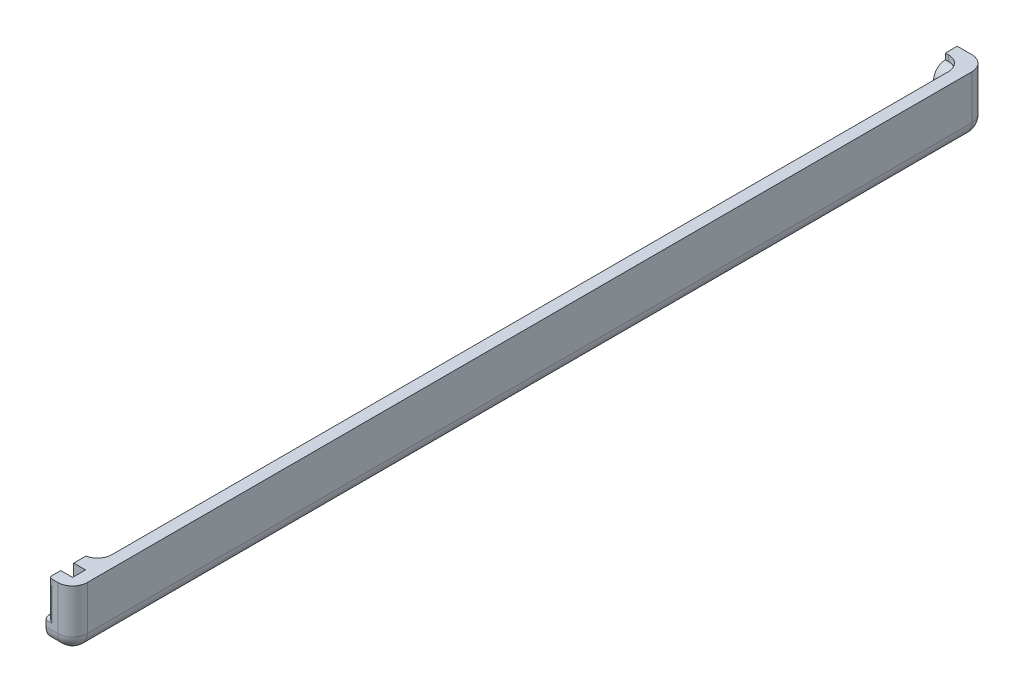
SolidWorks part; units mm, degrees
ref_plane "Front Plane" through (0, 0, 0) normal (0, 0, 1) x (1, 0, 0)
ref_plane "Top Plane" through (0, 0, 0) normal (0, 1, 0) x (1, 0, 0)
ref_plane "Right Plane" through (0, 0, 0) normal (1, 0, 0) x (0, 0, -1)
sketch "Sketch1" plane through (0, 0, 0) normal (0, 1, 0) x (1, 0, 0)
  line L1 (-19.5, 77.5) -> (19.5, 77.5)
  line L2 (-19.5, 77.5) -> (-19.5, -77.5)
  line L3 (-19.5, -77.5) -> (19.5, -77.5)
  line L4 (19.5, 77.5) -> (19.5, -77.5)
  line L5 (-19.5, 77.5) -> (19.5, -77.5) construction
  line L6 (-19.5, -77.5) -> (19.5, 77.5) construction
  point P0 (0, 0)
  dimension "D1" = 39
  dimension "D2" = 155
extrude "Boss-Extrude1" add sketch "Sketch1" along normal blind 2
sketch "Sketch2" plane through (0, 2, 0) normal (0, 1, 0) x (1, 0, 0)
  line L0 (-17.5, -75.5) -> (-17.5, -77.5)
  line L1 (-19.5, 77.5) -> (19.5, 77.5)
  line L2 (-19.5, 77.5) -> (-19.5, -77.5)
  line L3 (-19.5, -77.5) -> (19.5, -77.5)
  line L4 (19.5, 77.5) -> (19.5, -77.5)
  line L5 (-17.5, 75.5) -> (17.5, 75.5)
  line L6 (-17.5, 75.5) -> (-17.5, -75.5)
  line L7 (-17.5, -75.5) -> (17.5, -75.5)
  line L8 (17.5, 75.5) -> (17.5, -75.5)
  line L9 (-17.5, 75.5) -> (17.5, -75.5) construction
  line L10 (-17.5, -75.5) -> (17.5, 75.5) construction
  line L11 (17.5, -75.5) -> (17.5, -77.5)
  point P6 (0, 0)
  line M9 (19.5, -77.5) -> (19.5, 77.5)
  line M10 (19.5, 77.5) -> (-19.5, 77.5)
  line M11 (-19.5, 77.5) -> (-19.5, -77.5)
  line M12 (-19.5, -77.5) -> (19.5, -77.5)
  dimension "D1" = 2
  dimension "D2" = 2
extrude "Boss-Extrude2" add sketch "Sketch2" along normal blind 38 contours L8 L11 L3 L0 L6 L5 M9 M10 M11 M12 region at (-19.0983, 2, 76.5)
sketch "Sketch3" plane through (0, 2, 0) normal (0, 1, 0) x (1, 0, 0)
  line L0 (-17.5, 75.5) -> (-17.5, -77.5) construction
  line L1 (-17.5, -77.5) -> (-15.5, -77.5)
  line L2 (-17.5, -77.5) -> (-17.5, -75.5)
  line L3 (-17.5, -75.5) -> (-15.5, -75.5)
  line L4 (-15.5, -77.5) -> (-15.5, -75.5)
  line L5 (-17.5, -73.3) -> (-15.5, -73.3)
  line L6 (-17.5, -73.3) -> (-17.5, -71.3)
  line L7 (-17.5, -71.3) -> (-15.5, -71.3)
  line L8 (-15.5, -73.3) -> (-15.5, -71.3)
  line L9 (17.5, 75.5) -> (17.5, -77.5) construction
  line L10 (17.5, -77.5) -> (15.5, -77.5)
  line L11 (17.5, -77.5) -> (17.5, -75.5)
  line L12 (17.5, -75.5) -> (15.5, -75.5)
  line L13 (15.5, -77.5) -> (15.5, -75.5)
  line L14 (17.5, -73.3) -> (15.5, -73.3)
  line L15 (17.5, -73.3) -> (17.5, -71.3)
  line L16 (17.5, -71.3) -> (15.5, -71.3)
  line L17 (15.5, -73.3) -> (15.5, -71.3)
  line L18 (15.5, -75.5) -> (15.5, -73.3) construction
  line L19 (-15.5, -73.3) -> (15.5, -73.3) construction
  line L20 (-15.5, -75.5) -> (-15.5, -73.3) construction
  line L21 (-15.5, -75.5) -> (15.5, -75.5) construction
  line L22 (15.5, -71.3) -> (-15.5, -71.3) construction
  dimension "D1" = 2
  dimension "D2" = 2
  dimension "D3" = 2.2
  dimension "D4" = 2
extrude "Boss-Extrude3" add sketch "Sketch3" along normal up to surface (38 mm away) up to face at (0, 40, 0.5)
sketch "Sketch4" plane through (0, 0, -75.5) normal (0, 0, 1) x (1, 0, 0)
  line L0 (-17.5, 40) -> (-15.5, 40)
  line L1 (-17.5, 40) -> (17.5, 40) construction
  line L2 (-15.5, 40) -> (-15.5, 38)
  line L3 (-15.5, 38) -> (-17.5, 38)
  line L5 (-17.5, 38) -> (-17.5, 40)
  line L7 (-17.5, 40) -> (-17.5, 2) construction
  line L8 (-15.5, 33.8) -> (-17.5, 31.8)
  line L9 (-17.5, 31.8) -> (-17.5, 35.8)
  line L10 (-15.5, 33.8) -> (-15.5, 35.8)
  line L11 (-15.5, 35.8) -> (-17.5, 35.8)
  line L12 (0, 0) -> (0, 40) construction
  line L13 (15.5, 35.8) -> (17.5, 35.8)
  line L14 (15.5, 33.8) -> (15.5, 35.8)
  line L15 (17.5, 31.8) -> (17.5, 35.8)
  line L16 (15.5, 33.8) -> (17.5, 31.8)
  line L17 (17.5, 38) -> (17.5, 40)
  line L18 (15.5, 38) -> (17.5, 38)
  line L19 (15.5, 40) -> (15.5, 38)
  line L20 (17.5, 40) -> (15.5, 40)
  dimension "D1" = 2
  dimension "D2" = 2
  dimension "D3" = 45
  dimension "D4" = 2.2
  dimension "D5" = 2
extrude "Boss-Extrude4" add sketch "Sketch4" along normal up to surface (153 mm away) up to face at (0, 20.5, 77.5)
sketch "Sketch5" plane through (0, 2, 0) normal (0, 1, 0) x (1, 0, 0)
  line L1 (-15.5, -77.5) -> (15.5, -77.5)
  line L2 (-15.5, -77.5) -> (-15.5, -75.5)
  line L3 (-15.5, -75.5) -> (15.5, -75.5)
  line L4 (15.5, -77.5) -> (15.5, -75.5)
  line L5 (-15.5, -71.3) -> (15.5, -71.3)
  line L6 (-15.5, -71.3) -> (-15.5, -73.3)
  line L7 (-15.5, -73.3) -> (15.5, -73.3)
  line L8 (15.5, -71.3) -> (15.5, -73.3)
sketch "Sketch6" plane through (0, 0, -75.5) normal (0, 0, 1) x (1, 0, 0)
  line L0 (-17.5, 38) -> (-15.5, 38) construction
  line L1 (-17.5, 38) -> (17.5, 38)
  line L2 (-17.5, 38) -> (-17.5, 35.8)
  line L3 (-17.5, 35.8) -> (17.5, 35.8)
  line L4 (17.5, 38) -> (17.5, 35.8)
  line L5 (-17.5, 38) -> (-17.5, 35.8) construction
  line L6 (-15.5, 35.8) -> (-17.5, 35.8) construction
extrude "Cut-Extrude1" cut sketch "Sketch6" along normal through all
sketch "Sketch7" plane through (0, 2, 0) normal (0, 1, 0) x (1, 0, 0)
  line L1 (-17.5, -75.5) -> (17.5, -75.5)
  line L2 (-17.5, -75.5) -> (-17.5, -73.3)
  line L3 (-17.5, -73.3) -> (17.5, -73.3)
  line L4 (17.5, -75.5) -> (17.5, -73.3)
extrude "Cut-Extrude2" cut sketch "Sketch7" along normal through all
extrude "Boss-Extrude5" add sketch "Sketch5" along normal blind 2
sketch "Sketch8" plane through (0, 0, 0) normal (1, 0, 0) x (0, 0, -1)
  line L0 (75.5, 40) -> (73.5, 40)
  line L1 (-73.3, 40) -> (75.5, 40) construction
  line L2 (73.5, 40) -> (73.5, 38)
  line L3 (-73.3, 38) -> (75.5, 38) construction
  line L4 (73.5, 38) -> (75.5, 38)
  line L5 (75.5, 38) -> (75.5, 40)
  line L6 (75.5, 35.8) -> (73.5, 35.8)
  line L7 (-73.3, 35.8) -> (75.5, 35.8) construction
  line L8 (73.5, 35.8) -> (73.5, 33.8)
  line L9 (-71.3, 33.8) -> (75.5, 33.8) construction
  line L10 (73.5, 33.8) -> (75.5, 31.8)
  line L11 (75.5, 31.8) -> (75.5, 35.8)
  dimension "D1" = 2
extrude "Boss-Extrude6" add sketch "Sketch8" along normal up to surface and the other way up to surface up to face at (17.5, 16.9, -2.1) other way up to face at (-17.5, 16.9, -2.1)
sketch "Sketch10" plane through (-17.5, 0, 0) normal (1, 0, 0) x (0, 0, -1)
  line L1 (-75.5, 35.8) -> (-77.5, 35.8)
  line L2 (-75.5, 35.8) -> (-75.5, 38)
  line L3 (-75.5, 38) -> (-77.5, 38)
  line L4 (-77.5, 35.8) -> (-77.5, 38)
  line L5 (-73.3, 40) -> (-75.5, 40)
  line L6 (-73.3, 40) -> (-73.3, 38)
  line L7 (-73.3, 38) -> (-75.5, 38)
  line L8 (-75.5, 40) -> (-75.5, 38)
  line M1 (-75.5, 40) -> (-75.5, 38)
  line M2 (-75.5, 38) -> (-77.5, 38)
  line M3 (-77.5, 38) -> (-77.5, 35.8)
  line M4 (-77.5, 35.8) -> (-75.5, 35.8)
  line M11 (-73.3, 38) -> (-73.3, 40)
  line M12 (-73.3, 40) -> (-75.5, 40)
extrude "Boss-Extrude8" add sketch "Sketch10" along normal up to surface (2 mm away) contours L2 M4 M2 M3 | L7 M11 M12 M1 region at (-17.5, 39, 74.4) region at (-17.5, 36.9, 76.5) up to face at (-15.5, 39, -0.1)
sketch "Sketch11" plane through (17.5, 0, 0) normal (-1, 0, 0) x (0, 0, 1)
  line L1 (75.5, 35.8) -> (77.5, 35.8)
  line L2 (75.5, 35.8) -> (75.5, 38)
  line L3 (75.5, 38) -> (77.5, 38)
  line L4 (77.5, 35.8) -> (77.5, 38)
  line L5 (73.3, 40) -> (75.5, 40)
  line L6 (73.3, 40) -> (73.3, 38)
  line L7 (73.3, 38) -> (75.5, 38)
  line L8 (75.5, 40) -> (75.5, 38)
  line M2 (75.5, 35.8) -> (77.5, 35.8)
  line M3 (77.5, 35.8) -> (77.5, 38)
  line M4 (77.5, 38) -> (75.5, 38)
  line M5 (75.5, 38) -> (75.5, 40)
  line M6 (75.5, 40) -> (73.3, 40)
  line M7 (73.3, 40) -> (73.3, 38)
extrude "Boss-Extrude9" add sketch "Sketch11" along normal up to surface (2 mm away) contours L2 M2 M3 M4 | L7 M7 M5 M6 region at (17.5, 36.9, 76.5) region at (17.5, 39, 74.4) up to face at (15.5, 39, -0.1)
fillet "Fillet2" radius 2.5 17 edges at (-17.5, 16.9, 71.3) (17.5, 16.9, 71.3) (19.5, 20, 77.5) (-19.5, 20, 77.5) (-19.5, 20, -77.5) (-17.5, 16.9, -75.5) (17.5, 16.9, -75.5) (19.5, 20, -77.5) (-19.5, 40, 0) (0, 40, -77.5) (19.5, 40, 0) (0, 0, -77.5) (0, 0, 77.5) (-19.5, 0, 0) (19.5, 0, 0) (-17.5, 40, 77.5) (17.5, 40, 77.5)
sketch "Sketch13" plane through (0, 0, -77.5) normal (0, 0, -1) x (-1, 0, 0)
  line L0 (15.5, 37.5) -> (15.5, 4) construction
  line L1 (-15.5, 7) -> (15.5, 7)
  line L2 (-15.5, 7) -> (-15.5, 4)
  line L3 (-15.5, 4) -> (15.5, 4)
  line L4 (15.5, 7) -> (15.5, 4)
  dimension "D1" = 3
sketch "Sketch14" plane through (0, 0, -75.5) normal (0, 0, 1) x (1, 0, 0)
  line L1 (-18.25, 9) -> (18.25, 9)
  line L2 (-18.25, 9) -> (-18.25, 1.25)
  line L3 (-18.25, 1.25) -> (18.25, 1.25)
  line L4 (18.25, 9) -> (18.25, 1.25)
  line L5 (15.5, 7) -> (-15.5, 7) construction
  line L7 (17, 0) -> (17, 2.5) construction
  line L8 (19.5, 2.5) -> (17, 2.5) construction
  line L10 (-19.5, 2.5) -> (-17, 2.5) construction
  point P20 (17, 1.25)
  point P23 (18.25, 2.5)
  point P26 (-18.25, 2.5)
  dimension "D1" = 2
extrude "Boss-Extrude10" add sketch "Sketch14" along normal blind 2
extrude "Cut-Extrude4" cut sketch "Sketch13" against normal blind 2
fillet "Fillet3" radius 2 1 edges at (0, 9, -73.5)
fillet "Fillet4" radius 0.5 12 edges at (0, 4, -77.5) (0, 7, -77.5) (15.5, 7, -76.5) (15.5, 4, -76.5) (15.5, 5.5, -77.5) (-15.5, 4, -76.5) (-15.5, 7, -76.5) (-15.5, 5.5, -77.5) (0, 7, -75.5) (-15.5, 5.5, -75.5) (0, 4, -75.5) (15.5, 5.5, -75.5)
sketch "Sketch15" plane through (0, 0, 0) normal (0, -1, 0) x (1, 0, 0)
  line L0 (0, 77.5) -> (0, 0) construction
  line L1 (-17, 77.5) -> (17, 77.5) construction
  line L2 (0, 0) -> (0, -77.5) construction
  line L4 (17, -77.5) -> (-17, -77.5) construction
  circle A0 centre (0, 38.75) radius 5.1
  circle A1 centre (0, -38.75) radius 5.1
  dimension "D1" = 10.2
extrude "Cut-Extrude5" cut sketch "Sketch15" against normal through all
sketch "Sketch16" plane through (0, 2, 0) normal (0, 1, 0) x (1, 0, 0)
  circle A0 centre (0, 38.75) radius 7.1
  circle A1 centre (0, -38.75) radius 7.1
  circle A2 centre (0, 38.75) radius 5.1 construction
  dimension "D1" = 2
extrude "Boss-Extrude11" add sketch "Sketch16" along normal blind 1
fillet "Fillet5" radius 0.5 4 edges at (0, 2, 45.85) (0, 2, -31.65) (0, 3, 45.85) (0, 3, -31.65)
sketch "Sketch12" plane through (0, 0, -75.5) normal (0, 0, 1) x (1, 0, 0)
  line L0 (0, 0) -> (0, 40) construction
  line L1 (15.5, 40) -> (-15.5, 40) construction
  line L2 (0, 20) -> (-10, 20)
  line L3 (0, 20) -> (-9.0097, 15.6612)
  line L4 (0, 20) -> (-6.2349, 12.1817)
  line L5 (0, 20) -> (-2.2252, 10.2507)
  line L6 (0, 20) -> (2.2252, 10.2507)
  line L7 (0, 20) -> (6.2349, 12.1817)
  line L8 (0, 20) -> (9.0097, 15.6612)
  line L9 (0, 20) -> (10, 20)
  line L10 (0, 20) -> (9.0097, 24.3388)
  line L11 (0, 20) -> (6.2349, 27.8183)
  line L12 (0, 20) -> (2.2252, 29.7493)
  line L13 (0, 20) -> (-2.2252, 29.7493)
  line L14 (0, 20) -> (-6.2349, 27.8183)
  line L15 (0, 20) -> (-9.0097, 24.3388)
  circle A0 centre (0, 20) radius 10
  circle A1 centre (0, 20) radius 7.5
  circle A2 centre (0, 20) radius 5
  circle A3 centre (0, 20) radius 2.5
  point P26 (0, 20)
  dimension "D1" = 20
  dimension "D2" = 2.5
  dimension "D3" = 2.5
  dimension "D4" = 2.5
  dimension "D5" = 14
extrude "Cut-Extrude3" cut sketch "Sketch12" against normal through all contours A1 L6 A0 L7 | A1 L4 A0 L5 | A1 L2 A0 L3 | A1 L14 A0 L15 | A1 L0 A0 L13 | L0 A1 L12 A0 | A1 L10 A0 L11 | A1 L8 A0 L9 | A3 L8 A2 L9 | A3 L10 A2 L11 | L0 A3 L12 A2 | A3 L0 A2 L13 | A3 L14 A2 L15 | A3 L2 A2 L3 | A3 L4 A2 L5 | A3 L6 A2 L7 region at (-3.7903, 12.1293, -75.5) region at (3.7903, 12.1293, -75.5) region at (-1.6732, 16.5256, -75.5) region at (1.6732, 16.5256, -75.5) region at (-8.5168, 18.0561, -75.5) region at (8.5168, 18.0561, -75.5) region at (-0.4345, 23.8563, -75.5) region at (0.4345, 23.8563, -75.5) region at (-3.7596, 19.1419, -75.5) region at (3.7596, 19.1419, -75.5) region at (3.015, 22.4044, -75.5) region at (-3.015, 22.4044, -75.5) region at (-6.8299, 25.4467, -75.5) region at (6.8299, 25.4467, -75.5) region at (-0.9843, 28.7358, -75.5) region at (0.9843, 28.7358, -75.5)
fillet "Fillet6" radius 0.4 112 edges at (5.4555, 26.841, -77.5) (7.8183, 26.2349, -77.5) (7.8835, 23.7965, -77.5) (5.8637, 24.6762, -77.5) (3.75, 20, -77.5) (4.8746, 18.8874, -77.5) (3.3786, 18.3729, -77.5) (2.4373, 19.4437, -77.5) (-1.9471, 28.5306, -77.5) (0, 30, -77.5) (1.9471, 28.5306, -77.5) (0, 27.5, -77.5) (-7.8835, 16.2035, -77.5) (-9.7493, 17.7748, -77.5) (-8.75, 20, -77.5) (-7.312, 18.3311, -77.5) (2.3381, 17.0681, -77.5) (2.1694, 15.4952, -77.5) (0.8345, 16.344, -77.5) (1.0847, 17.7476, -77.5) (-0.8345, 16.344, -77.5) (-2.1694, 15.4952, -77.5) (-2.3381, 17.0681, -77.5) (-1.0847, 17.7476, -77.5) (5.4555, 13.159, -77.5) (4.3388, 10.9903, -77.5) (1.9471, 11.4694, -77.5) (3.2541, 13.2427, -77.5) (0, 22.5, -77.5) (-0.8345, 23.656, -77.5) (0, 25, -77.5) (0.8345, 23.656, -77.5) (-3.3786, 21.6271, -77.5) (-3.9092, 23.1174, -77.5) (-2.3381, 22.9319, -77.5) (-1.9546, 21.5587, -77.5) (-3.3786, 18.3729, -77.5) (-4.8746, 18.8874, -77.5) (-3.75, 20, -77.5) (-2.4373, 19.4437, -77.5) (-1.9471, 11.4694, -77.5) (-4.3388, 10.9903, -77.5) (-5.4555, 13.159, -77.5) (-3.2541, 13.2427, -77.5) (-7.8835, 23.7965, -77.5) (-7.8183, 26.2349, -77.5) (-5.4555, 26.841, -77.5) (-5.8637, 24.6762, -77.5) (2.3381, 22.9319, -77.5) (3.9092, 23.1174, -77.5) (3.3786, 21.6271, -77.5) (1.9546, 21.5587, -77.5) (8.75, 20, -77.5) (9.7493, 17.7748, -77.5) (7.8835, 16.2035, -77.5) (7.312, 18.3311, -77.5) (7.8835, 23.7965, -75.5) (7.8183, 26.2349, -75.5) (5.4555, 26.841, -75.5) (5.8637, 24.6762, -75.5) (3.3786, 18.3729, -75.5) (4.8746, 18.8874, -75.5) (3.75, 20, -75.5) (2.4373, 19.4437, -75.5) (1.9471, 28.5306, -75.5) (0, 30, -75.5) (-1.9471, 28.5306, -75.5) (0, 27.5, -75.5) (-8.75, 20, -75.5) (-9.7493, 17.7748, -75.5) (-7.8835, 16.2035, -75.5) (-7.312, 18.3311, -75.5) (0.8345, 16.344, -75.5) (2.1694, 15.4952, -75.5) (2.3381, 17.0681, -75.5) (1.0847, 17.7476, -75.5) (-2.3381, 17.0681, -75.5) (-2.1694, 15.4952, -75.5) (-0.8345, 16.344, -75.5) (-1.0847, 17.7476, -75.5) (1.9471, 11.4694, -75.5) (4.3388, 10.9903, -75.5) (5.4555, 13.159, -75.5) (3.2541, 13.2427, -75.5) (0, 22.5, -75.5) (0.8345, 23.656, -75.5) (0, 25, -75.5) (-0.8345, 23.656, -75.5) (-2.3381, 22.9319, -75.5) (-3.9092, 23.1174, -75.5) (-3.3786, 21.6271, -75.5) (-1.9546, 21.5587, -75.5) (-3.75, 20, -75.5) (-4.8746, 18.8874, -75.5) (-3.3786, 18.3729, -75.5) (-2.4373, 19.4437, -75.5) (-5.4555, 13.159, -75.5) (-4.3388, 10.9903, -75.5) (-1.9471, 11.4694, -75.5) (-3.2541, 13.2427, -75.5) (-5.4555, 26.841, -75.5) (-7.8183, 26.2349, -75.5) (-7.8835, 23.7965, -75.5) (-5.8637, 24.6762, -75.5) (3.3786, 21.6271, -75.5) (3.9092, 23.1174, -75.5) (2.3381, 22.9319, -75.5) (7.8835, 16.2035, -75.5) (9.7493, 17.7748, -75.5) (8.75, 20, -75.5) (7.312, 18.3311, -75.5) (1.9546, 21.5587, -75.5)
fillet "Fillet7" radius 0.5 8 edges at (15.5, 40, 0.75) (15.5, 39.2678, 76.7678) (-15.5, 40, 0.75) (-15.5, 39.2678, 76.7678) (0, 40, -73.5) (15.5, 20.75, 77.5) (-15.5, 20.75, 77.5) (0, 4, 77.5)
sketch "Sketch17" plane through (0, 0, 0) normal (0, -1, 0) x (1, 0, 0)
  line L0 (-17, -77.5) -> (-17, 70.3)
  line L1 (-17, -77.5) -> (17, -77.5)
  line L2 (17, -77.5) -> (17, 70.3)
  line L3 (17, -75) -> (17, 75) construction
  line L5 (17, 70.3) -> (15, 71.3)
  line L6 (15, 71.3) -> (15, 77.5)
  line L7 (15, 77.5) -> (-15, 77.5)
  line L8 (-15, 77.5) -> (-15, 71.3)
  line L9 (-15, 71.3) -> (-17, 70.3)
  line L10 (-17, 75) -> (-17, -75) construction
  line L12 (-15, 71.3) -> (15, 71.3) construction
  line L13 (17, 70.3) -> (-17, 70.3) construction
  line L14 (0, 71.3) -> (0, 77.5) construction
  line L15 (-17, 77.5) -> (17, 77.5) construction
  arc A0 (-19.5, -75) -> (-17, -77.5) centre (-17, -75) ccw construction
  dimension "D1" = 1
  dimension "D2" = 30
  dimension "D3" = 6.2
extrude "Cut-Extrude6" cut sketch "Sketch17" against normal blind 6
sketch "Sketch18" plane through (0, 0, 0) normal (0, 0, 1) x (1, 0, 0)
  line L0 (15, 9) -> (-15, 9) construction
  line L1 (-14.5, 9) -> (14.5, 9)
  line L2 (-14.5, 9) -> (-14.5, 6)
  line L3 (-14.5, 6) -> (14.5, 6)
  line L4 (14.5, 9) -> (14.5, 6)
  line L5 (-17, 6) -> (17, 6) construction
  line L6 (0, 6) -> (0, 0) construction
  dimension "D1" = 29
extrude "Cut-Extrude8" cut sketch "Sketch18" against normal through all
sketch "Sketch20" plane through (0, 0, 0) normal (0, 0, 1) x (1, 0, 0)
  line L0 (-16, 40) -> (16, 40) construction
  line L1 (-19.5, 40) -> (-14.5, 40)
  line L2 (-19.5, 40) -> (-19.5, 0)
  line L3 (-19.5, 0) -> (-14.5, 0)
  line L4 (-14.5, 40) -> (-14.5, 0)
  line L5 (-14.5, 6) -> (14.5, 6)
  line L6 (-14.5, 6) -> (-14.5, 40)
  line L7 (-14.5, 40) -> (14.5, 40)
  line L8 (14.5, 6) -> (14.5, 40)
  line L9 (14.5, 40) -> (19.5, 40)
  line L10 (14.5, 40) -> (14.5, 0)
  line L11 (14.5, 0) -> (19.5, 0)
  line L12 (19.5, 40) -> (19.5, 0)
  line L13 (-15, 0) -> (-17, 0) construction
  line L14 (-19.5, 2.5) -> (-19.5, 37.5) construction
  line L15 (17, 0) -> (15, 0) construction
  line L16 (19.5, 37.5) -> (19.5, 2.5) construction
extrude "Cut-Extrude11" cut sketch "Sketch20" against normal through all both and the other way through all contours L5 L8 L7 L4 | L1 L2 L3 L4 region at (0, 23, 0)
sketch "Sketch21" plane through (0, 0, 0) normal (1, 0, 0) x (0, 0, -1)
  line L1 (-77.5, 40) -> (77.5, 40)
  line L2 (-77.5, 40) -> (-77.5, 30)
  line L3 (-77.5, 30) -> (77.5, 30)
  line L4 (77.5, 40) -> (77.5, 30)
  line L5 (77.5, 30) -> (-77.5, 30)
  line L6 (77.5, 30) -> (77.5, 10)
  line L7 (77.5, 10) -> (-77.5, 10)
  line L8 (-77.5, 30) -> (-77.5, 10)
  line L9 (-77.5, 10) -> (77.5, 10)
  line L10 (-77.5, 10) -> (-77.5, 0)
  line L11 (-77.5, 0) -> (77.5, 0)
  line L12 (77.5, 10) -> (77.5, 0)
  line L16 (77.5, 30) -> (77.5, 10)
  line L17 (-77.5, 10) -> (-77.5, 30)
  line L18 (77.5, 37.5) -> (77.5, 6) construction
  line L19 (-75, 40) -> (75, 40) construction
  line L20 (-77.5, 2.5) -> (-77.5, 37.5) construction
  line L21 (75, 0) -> (-70.3, 0) construction
  point P6 (78.7392, 41.1266)
  dimension "D1" = 20
  dimension "D2" = 10
extrude "Cut-Extrude12" cut sketch "Sketch21" along normal through all contours L3 L8 L7 L6 | L4 L1 L2 L3 region at (0, 35, 0) region at (0, 20, 0)
